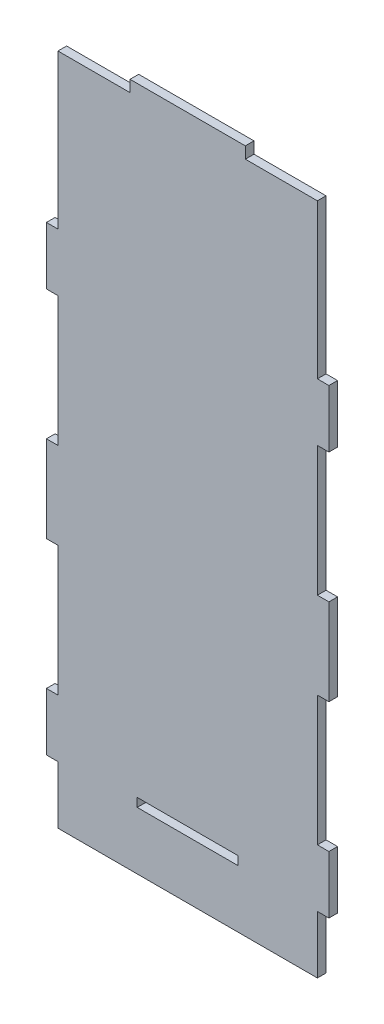
SolidWorks part; units mm, degrees
ref_plane "Front" through (0, 0, 0) normal (0, 0, 1) x (1, 0, 0)
ref_plane "Top" through (0, 0, 0) normal (0, 1, 0) x (1, 0, 0)
ref_plane "Right" through (0, 0, 0) normal (1, 0, 0) x (0, 0, -1)
sketch "Sketch1" plane through (0, 0, 0) normal (0, 0, 1) x (1, 0, 0)
  line L1 (0, 0) -> (90, 0)
  line L2 (0, 0) -> (0, 200)
  line L3 (0, 200) -> (90, 200)
  line L4 (90, 0) -> (90, 200)
  dimension "D1" = 90
  dimension "D2" = 200
extrude "Boss-Extrude1" add sketch "Sketch1" along normal blind 3
sketch "Sketch2" plane through (0, 0, 3) normal (0, 0, 1) x (1, 0, 0)
  line L0 (0, 180) -> (-23, 180)
  line L1 (0, 180) -> (0, 160)
  line L2 (0, 200) -> (0, 0) construction
  line L3 (90, 200) -> (0, 200) construction
  line L4 (-23, 180) -> (-23, 160)
  line L5 (-23, 160) -> (0, 160)
  line L6 (0, 0) -> (90, 0) construction
  line L7 (0, 115) -> (-23, 115)
  line L8 (-23, 115) -> (-23, 85)
  line L9 (-23, 85) -> (0, 85)
  line L10 (0, 40) -> (-23, 40)
  line L11 (-23, 40) -> (-23, 20)
  line L12 (-23, 20) -> (0, 20)
  line L13 (90, 180) -> (113, 180)
  line L14 (90, 0) -> (90, 200) construction
  line L15 (0, 115) -> (0, 85)
  line L16 (113, 180) -> (113, 160)
  line L17 (113, 160) -> (90, 160)
  line L18 (90, 115) -> (113, 115)
  line L19 (113, 115) -> (113, 85)
  line L20 (113, 85) -> (90, 85)
  line L21 (90, 40) -> (113, 40)
  line L22 (113, 40) -> (113, 20)
  line L23 (113, 20) -> (90, 20)
  line L24 (0, 40) -> (0, 20)
  line L25 (90, 40) -> (90, 20)
  line L26 (90, 85) -> (90, 115)
  line L27 (90, 180) -> (90, 160)
  circle A0 centre (-11.5, 170) radius 2.5
  circle A1 centre (101.5, 170) radius 2.5
  circle A2 centre (101.5, 100) radius 2.5
  circle A3 centre (-11.5, 100) radius 2.5
  circle A4 centre (-11.5, 30) radius 2.5
  circle A5 centre (101.5, 30) radius 2.5
  point P40 (-23, 170)
  point P41 (-23, 100)
  point P42 (0, 100)
  point P43 (-23, 30)
  point P44 (-11.5, 180)
  point P45 (101.5, 180)
  line M21 (0, 200) -> (0, 0)
  line M23 (90, 0) -> (90, 200)
  dimension "D3" = 20
  dimension "D4" = 30
  dimension "D5" = 20
  dimension "D6" = 5
  dimension "D7" = 5
  dimension "D8" = 5
  dimension "D9" = 5
  dimension "D10" = 5
  dimension "D11" = 5
  dimension "D1" = 23
  dimension "D2" = 23
  dimension "D12" = 20
  dimension "D13" = 20
sketch "Sketch3" plane through (0, 0, 3) normal (0, 0, 1) x (1, 0, 0)
  line L0 (0, 200) -> (0, 0) construction
  line L1 (-3, 180) -> (0, 180)
  line L2 (-3, 180) -> (-3, 160)
  line L3 (-3, 160) -> (0, 160)
  line L4 (0, 180) -> (0, 160)
  line L5 (90, 180) -> (93, 180)
  line L6 (90, 180) -> (90, 160)
  line L7 (90, 160) -> (93, 160)
  line L8 (93, 180) -> (93, 160)
  line L9 (90, 115) -> (93, 115)
  line L10 (90, 115) -> (90, 85)
  line L11 (90, 85) -> (93, 85)
  line L12 (93, 115) -> (93, 85)
  line L13 (0, 115) -> (-3, 115)
  line L14 (0, 115) -> (0, 85)
  line L15 (0, 85) -> (-3, 85)
  line L16 (-3, 115) -> (-3, 85)
  line L17 (-3, 40) -> (0, 40)
  line L18 (-3, 40) -> (-3, 20)
  line L19 (-3, 20) -> (0, 20)
  line L20 (0, 40) -> (0, 20)
  line L21 (90, 40) -> (93, 40)
  line L22 (90, 40) -> (90, 20)
  line L23 (90, 20) -> (93, 20)
  line L24 (93, 40) -> (93, 20)
  line L25 (90, 0) -> (90, 200) construction
  line L26 (0, 100) -> (90, 100) construction
  line L27 (90, 200) -> (0, 200) construction
  line L28 (0, 0) -> (90, 0) construction
  point P30 (0, 100)
  dimension "D1" = 3
  dimension "D2" = 3
  dimension "D3" = 20
  dimension "D4" = 30
  dimension "D5" = 20
  dimension "D6" = 20
  dimension "D7" = 20
extrude "Boss-Extrude2" add sketch "Sketch3" against normal blind 3
extrude "Boss-Extrude3" add sketch "Sketch2" against normal blind 3 contours L4 L5 L0 A0 M21 | L17 L16 L13 A1 M23 | L20 L19 L18 A2 M23 | L8 L9 L7 A3 M21 | L11 L12 L10 A4 M21 | L23 L22 L21 A5 M23 region at (-0.3048, 170, 3) region at (-0.3048, 30, 3) region at (-0.378, 100, 3) region at (101.5, 39.6952, 3) region at (101.5, 114.622, 3) region at (101.5, 179.6952, 3)
sketch "Sketch4" plane through (0, 0, 3) normal (0, 0, 1) x (1, 0, 0)
  line L1 (0, 200) -> (90, 200)
  line L2 (0, 200) -> (0, 233.5)
  line L3 (0, 233.5) -> (90, 233.5)
  line L4 (90, 200) -> (90, 233.5)
  line L5 (25, 233.5) -> (65, 233.5)
  line L6 (25, 233.5) -> (25, 237.5)
  line L7 (25, 237.5) -> (65, 237.5)
  line L8 (65, 233.5) -> (65, 237.5)
  point P10 (45, 233.5)
  line M33 (90, 200) -> (0, 200)
  dimension "D1" = 33.5
  dimension "D2" = 4
  dimension "D3" = 40
extrude "Boss-Extrude4" add sketch "Sketch4" against normal blind 3 contours L4 L3 L2 M33 | L3 L8 L7 L6 region at (45, 216.75, 3) region at (45, 235.5, 3)
sketch "Sketch5" plane through (0, 0, 3) normal (0, 0, 1) x (1, 0, 0)
  line L1 (0, 0) -> (90, 0)
  line L2 (0, 0) -> (0, 20)
  line L3 (0, 20) -> (90, 20)
  line L4 (90, 0) -> (90, 20)
extrude "Cut-Extrude1" [suppressed] cut sketch "Sketch5" against normal blind 10
sketch "Sketch6" plane through (0, 0, 0) normal (0, 0, -1) x (-1, 0, 0)
  line L0 (-113, 180) -> (-90, 180) construction
  line L1 (-113, 180) -> (-94, 180)
  line L2 (-113, 180) -> (-113, 20)
  line L3 (-113, 20) -> (-94, 20)
  line L4 (-94, 180) -> (-94, 20)
  line L5 (23, 180) -> (4, 180)
  line L6 (23, 180) -> (23, 20)
  line L7 (23, 20) -> (4, 20)
  line L8 (4, 180) -> (4, 20)
  line L12 (23, 20) -> (0, 20) construction
  line L13 (-90, 180) -> (-90, 233.5) construction
  line L14 (0, 233.5) -> (0, 180) construction
  line L15 (-113, 180) -> (-113, 160) construction
  line L16 (23, 180) -> (23, 160) construction
  dimension "D1" = 4
  dimension "D2" = 4
extrude "Cut-Extrude2" cut sketch "Sketch6" against normal blind 10
sketch "Sketch7" plane through (0, 0, 0) normal (0, 0, -1) x (-1, 0, 0)
  line L1 (-62.5, 23) -> (-27.5, 23)
  line L2 (-62.5, 23) -> (-62.5, 20)
  line L3 (-62.5, 20) -> (-27.5, 20)
  line L4 (-27.5, 23) -> (-27.5, 20)
  line L5 (-90, 20) -> (0, 20) construction
  point P8 (-45, 20)
  dimension "D1" = 3
  dimension "D2" = 35
extrude "Cut-Extrude3" cut sketch "Sketch7" against normal blind 4
sketch "Sketch8" [suppressed] plane through (0, 0, 0) normal (0, 0, -1) x (-1, 0, 0)
  line L0 (0, 0) -> (-90, 0) construction
  line L1 (-94, 169) -> (-90, 169)
  line L2 (-94, 169) -> (-94, 139)
  line L3 (-94, 139) -> (-90, 139)
  line L4 (-90, 169) -> (-90, 139)
  line L5 (-94, 109) -> (-90, 109)
  line L6 (-94, 109) -> (-94, 79)
  line L7 (-94, 79) -> (-90, 79)
  line L8 (-90, 109) -> (-90, 79)
  line L9 (-94, 49) -> (-90, 49)
  line L10 (-94, 49) -> (-94, 19)
  line L11 (-94, 19) -> (-90, 19)
  line L12 (-90, 49) -> (-90, 19)
  line L13 (0, 169) -> (4, 169)
  line L14 (0, 169) -> (0, 139)
  line L15 (0, 139) -> (4, 139)
  line L16 (4, 169) -> (4, 139)
  line L17 (0, 109) -> (4, 109)
  line L18 (0, 109) -> (0, 79)
  line L19 (0, 79) -> (4, 79)
  line L20 (4, 109) -> (4, 79)
  line L21 (0, 49) -> (4, 49)
  line L22 (0, 49) -> (0, 19)
  line L23 (0, 19) -> (4, 19)
  line L24 (4, 49) -> (4, 19)
  line L25 (-90, 0) -> (-90, 200) construction
  line L26 (0, 200) -> (0, 0) construction
  dimension "D4" = 30
  dimension "D1" = 4
  dimension "D2" = 4
  dimension "D3" = 19
  dimension "D5" = 30
  dimension "D6" = 30
  dimension "D7" = 30
  dimension "D8" = 30
extrude "Boss-Extrude5" [suppressed] add sketch "Sketch8" against normal blind 3
sketch "Sketch9" [suppressed] plane through (0, 0, 0) normal (0, 0, -1) x (-1, 0, 0)
  line L0 (-90, 169) -> (-94, 169) construction
  line L1 (-90, 200) -> (0, 200)
  line L2 (-90, 200) -> (-90, 173)
  line L3 (-90, 173) -> (0, 173)
  line L4 (0, 200) -> (0, 173)
  dimension "D1" = 4
extrude "Cut-Extrude4" [suppressed] cut sketch "Sketch9" against normal blind 4
equation "\"D5@Sketch3\"=\"D3@Sketch3\""
equation "\"D2@Sketch3\"=\"D1@Sketch3\""
equation "\"D2@Sketch2\"=\"D1@Sketch2\""
equation "\"D7@Sketch2\"=\"D6@Sketch2\""
equation "\"D8@Sketch2\"=\"D6@Sketch2\""
equation "\"D11@Sketch2\"=\"D6@Sketch2\""
equation "\"D10@Sketch2\"=\"D6@Sketch2\""
equation "\"D9@Sketch2\"=\"D6@Sketch2\""
equation "\"D5@Sketch2\"=\"D3@Sketch2\""
equation "\"D13@Sketch2\"=\"D12@Sketch2\""
equation "\"D7@Sketch3\"=\"D6@Sketch3\""
equation "\"D2@Sketch6\"=\"D1@Sketch6\""
equation "\"D2@Sketch8\"=\"D1@Sketch8\""
equation "\"D6@Sketch8\"=\"D5@Sketch8\""
equation "\"D4@Sketch8\"=\"D5@Sketch8\""
equation "\"D7@Sketch8\"=\"D8@Sketch8\""
